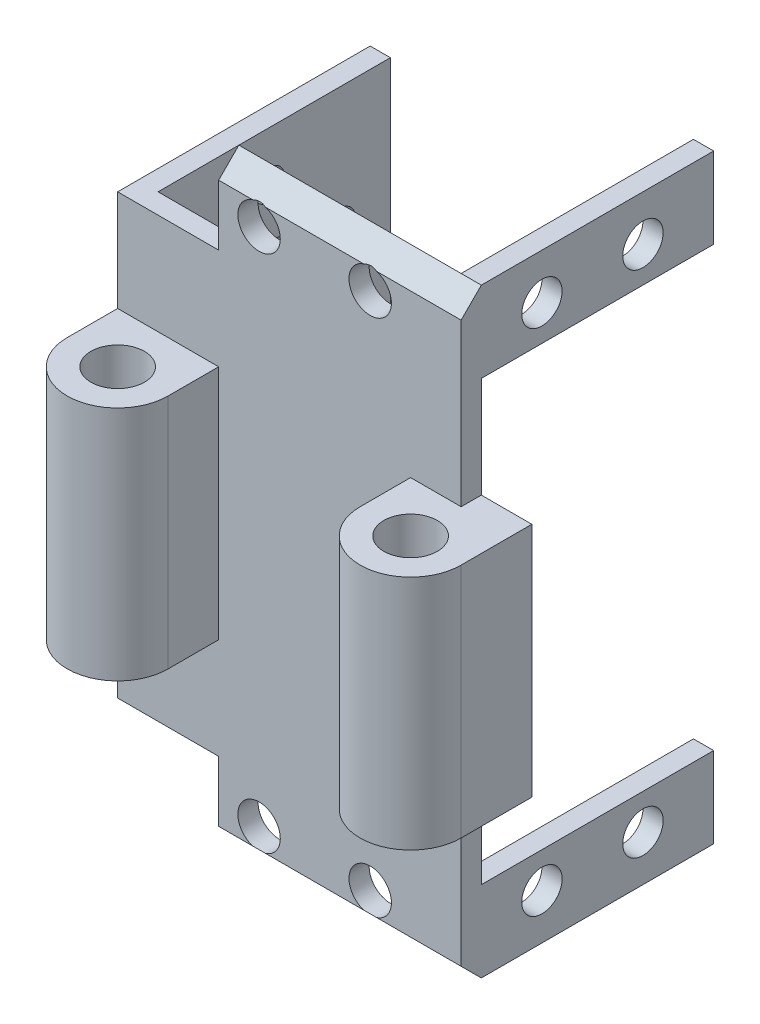
SolidWorks part; units mm, degrees
other "Marquage1"
sketch "Esquisse16" plane through (-20.25, -32.4, -23) normal (-0.063, -0.2594, -0.9637) x (0.9802, 0.1655, -0.1086)
ref_plane "Plan de face" through (0, 0, 0) normal (0, 0, 1) x (1, 0, 0)
ref_plane "Plan de dessus" through (0, 0, 0) normal (0, 1, 0) x (1, 0, 0)
ref_plane "Plan de droite" through (0, 0, 0) normal (1, 0, 0) x (0, 0, -1)
sketch "Esquisse1" plane through (0, 0, 0) normal (0, 0, 1) x (1, 0, 0)
  line L0 (8.75, 17) -> (8.75, 19)
  line L4 (16.25, -22.4) -> (16.25, 17)
  line L5 (8.75, 19) -> (-10.25, 19) construction
  line L6 (-10.25, 19) -> (-20.25, 19)
  line L7 (8.75, 19) -> (13.75, 19)
  line L8 (13.75, 19) -> (13.75, 27)
  line L9 (13.75, 27) -> (-10.25, 27)
  line L10 (-10.25, 27) -> (-10.25, 19)
  line L11 (-20.25, -2.7) -> (16.25, -2.7) construction
  line L17 (8.75, 17) -> (16.25, 17)
  line L20 (-20.25, 19) -> (-20.25, -24.4)
  line L21 (8.75, -22.4) -> (16.25, -22.4)
  line L22 (-10.25, -32.4) -> (-10.25, -24.4)
  line L23 (13.75, -32.4) -> (-10.25, -32.4)
  line L24 (13.75, -24.4) -> (13.75, -32.4)
  line L25 (8.75, -24.4) -> (13.75, -24.4)
  line L26 (-10.25, -24.4) -> (-20.25, -24.4)
  line L27 (8.75, -22.4) -> (8.75, -24.4)
  point P0 (0, 0)
  point P18 (0, -5.4)
  dimension "D1" = 19.7
  dimension "D2" = 21.7
  dimension "D3" = 24
  dimension "D4" = 8
  dimension "D5" = 5
  dimension "D6" = 2
  dimension "D7" = 10
  dimension "D8" = 36.5
extrude "Boss.-Extru.1" add sketch "Esquisse1" along normal blind 2
sketch "Esquisse2" plane through (0, 0, 0) normal (0, 0, -1) x (-1, 0, 0)
  line L0 (18.25, 19) -> (20.25, 19)
  line L1 (20.25, 19) -> (20.25, -24.4) construction
  line L2 (20.25, 19) -> (20.25, -24.4)
  line L3 (20.25, -24.4) -> (18.25, -24.4)
  line L5 (18.25, -24.4) -> (18.25, 19)
  line L9 (20.25, -24.4) -> (10.25, -24.4) construction
  dimension "D1" = 2
  dimension "D2" = 43.4
extrude "Boss.-Extru.2" add sketch "Esquisse2" along normal blind 23
sketch "Esquisse3" plane through (0, 27, 0) normal (0, 1, 0) x (1, 0, 0)
  line L0 (13.75, 0) -> (11.75, 0)
  line L1 (13.75, 0) -> (-10.25, 0) construction
  line L2 (11.75, 0) -> (11.75, 23)
  line L3 (11.75, 23) -> (13.75, 23)
  line L4 (13.75, 23) -> (13.75, 0)
  dimension "D1" = 2
  dimension "D2" = 23
extrude "Boss.-Extru.3" add sketch "Esquisse3" against normal blind 8
sketch "Esquisse8" plane through (0, -32.4, 0) normal (0, -1, 0) x (1, 0, 0)
  line L0 (13.75, 0) -> (11.75, 0)
  line L1 (11.75, 0) -> (11.75, -23)
  line L2 (11.75, -23) -> (13.75, -23)
  line L3 (13.75, -23) -> (13.75, 0)
  dimension "D1" = 2
extrude "Boss.-Extru.5" add sketch "Esquisse8" against normal blind 8
sketch "Esquisse9" plane through (13.75, 0, 0) normal (1, 0, 0) x (0, 0, -1)
  line L0 (-2, 19) -> (-2, 27) construction
  line L1 (-2, 19) -> (23, 19) construction
  line L2 (0, -2.7) -> (21.4042, -2.7) construction
  line L3 (0, -22.4) -> (0, 17) construction
  circle A0 centre (6, 22.5) radius 2
  circle A1 centre (16, 22.5) radius 2
  circle A2 centre (16, -27.9) radius 2
  circle A3 centre (6, -27.9) radius 2
  dimension "D1" = 4
  dimension "D2" = 4
  dimension "D3" = 10
  dimension "D4" = 3.5
  dimension "D5" = 3.5
  dimension "D6" = 8
extrude "Enlèv. mat.-Extru.3" cut sketch "Esquisse9" against normal blind 2
sketch "Esquisse10" plane through (-20.25, 0, 0) normal (-1, 0, 0) x (0, 0, 1)
  line L0 (-23, 19) -> (0, 19) construction
  line L1 (-23, -24.4) -> (-23, 19) construction
  line L2 (-23, -2.7) -> (2, -2.7) construction
  line L3 (2, 19) -> (2, -24.4) construction
  circle A0 centre (-11, 14.1) radius 1.5
  circle A1 centre (-11, 7.1) radius 2.25
  circle A2 centre (-4, 7.1) radius 1.5
  circle A3 centre (-11, 0.1) radius 1.5
  circle A4 centre (-18, 7.1) radius 1.5
  circle A5 centre (-11, -5.5) radius 1.5
  circle A6 centre (-11, -12.5) radius 2.25
  circle A7 centre (-4, -12.5) radius 1.5
  circle A8 centre (-18, -12.5) radius 1.5
  circle A9 centre (-11, -19.5) radius 1.5
  point P17 (-11, 7.1)
  dimension "D1" = 3
  dimension "D2" = 4.5
  dimension "D3" = 4.9
  dimension "D4" = 11.9
  dimension "D5" = 12
  dimension "D6" = 12
  dimension "D7" = 4
extrude "Enlèv. mat.-Extru.4" cut sketch "Esquisse10" against normal blind 2
sketch "Esquisse11" plane through (0, 0, 2) normal (0, 0, 1) x (1, 0, 0)
  line L0 (8.75, 19) -> (-10.25, 19) construction
  line L1 (-0.75, 19) -> (-0.75, 27) construction
  line L2 (13.75, 27) -> (-10.25, 27) construction
  line L3 (-6.25, 23) -> (4.75, 23) construction
  line L4 (16.25, -2.7) -> (-20.25, -2.7) construction
  line L5 (16.25, -22.4) -> (16.25, 17) construction
  line L6 (-20.25, 19) -> (-20.25, -24.4) construction
  circle A0 centre (-6.25, 23) radius 2.1
  circle A1 centre (4.75, 23) radius 2.1
  circle A2 centre (4.75, -28.4) radius 2.1
  circle A3 centre (-6.25, -28.4) radius 2.1
  point P11 (-0.75, 23)
  dimension "D2" = 4.2
  dimension "D3" = 4.2
  dimension "D1" = 11
extrude "Enlèv. mat.-Extru.5" cut sketch "Esquisse11" against normal up to next
sketch "Esquisse13" plane through (0, -24.4, 0) normal (0, -1, 0) x (1, 0, 0)
  line L0 (18.75, 12) -> (8.75, 2) construction
  line L1 (-10.25, 0) -> (-20.25, 0)
  line L2 (-10.25, 0) -> (-10.25, 7)
  line L4 (-20.25, 0) -> (-20.25, 7)
  line L5 (8.75, 0) -> (18.75, 0)
  line L6 (8.75, 0) -> (8.75, 7)
  line L8 (18.75, 0) -> (18.75, 7)
  line L9 (-10.25, 2) -> (-20.25, 12) construction
  circle A0 centre (13.75, 7) radius 2.65
  circle A1 centre (-15.25, 7) radius 2.65
  arc A2 (18.75, 7) -> (8.75, 7) centre (13.75, 7) ccw
  arc A3 (-10.25, 7) -> (-20.25, 7) centre (-15.25, 7) ccw
  dimension "D5" = 5.3
  dimension "D6" = 5.3
extrude "Boss.-Extru.6" add sketch "Esquisse13" against normal up to surface (43.4 mm away) up to face at (-16.25, 19, -7)
sketch "Esquisse14" plane through (0, 19, 0) normal (0, 1, 0) x (1, 0, 0)
  line L0 (13.75, -2) -> (13.75, 23) construction
  line L1 (-10.25, -2) -> (-20.25, -2)
  line L2 (-10.25, -2) -> (-10.25, -14.2809)
  line L3 (-10.25, -14.2809) -> (-24.6932, -14.2809)
  line L4 (-24.6932, -2) -> (-24.6932, -14.2809)
  line L5 (8.75, -2) -> (13.75, -2)
  line L6 (8.75, -2) -> (8.75, -13.0445)
  line L7 (8.75, -13.0445) -> (27.1122, -13.0445)
  line L8 (27.1122, -2) -> (27.1122, -13.0445)
  line L9 (13.75, 5.1811) -> (21.1699, 5.1811)
  line L10 (13.75, 5.1811) -> (13.75, -2)
  line L12 (21.1699, 5.1811) -> (21.1699, -2)
  line L13 (-20.25, -7) -> (-20.25, 23) construction
  line L14 (-20.25, 7.2947) -> (-22.7789, 7.2947)
  line L15 (-20.25, 7.2947) -> (-20.25, -2)
  line L17 (-22.7789, 7.2947) -> (-22.7789, -2)
  line L18 (-22.7789, -2) -> (-24.6932, -2)
  line L19 (21.1699, -2) -> (27.1122, -2)
extrude "Enlèv. mat.-Extru.6" cut sketch "Esquisse14" against normal blind 10
sketch "Esquisse15" plane through (0, -24.4, 0) normal (0, -1, 0) x (1, 0, 0)
  line L0 (-10.25, 2) -> (13.75, 2) construction
  line L1 (-7.7651, 2) -> (-20.25, 2)
  line L2 (-7.7651, 2) -> (-7.7651, 15.3144)
  line L3 (-7.7651, 15.3144) -> (-33.1794, 15.3144)
  line L4 (-33.1794, 2) -> (-33.1794, 15.3144)
  line L5 (13.75, 2) -> (13.75, -23) construction
  line L6 (6.631, 2) -> (13.75, 2)
  line L7 (6.631, 2) -> (6.631, 15.3144)
  line L8 (6.631, 15.3144) -> (24.5342, 15.3144)
  line L9 (24.5342, 2) -> (24.5342, 15.3144)
  line L11 (22.3035, 2) -> (22.3035, -6.0207)
  line L12 (22.3035, -6.0207) -> (13.75, -6.0207)
  line L13 (13.75, 2) -> (13.75, -6.0207)
  line L14 (-20.25, 7) -> (-20.25, -23) construction
  line L15 (-20.25, -7.2219) -> (-27.574, -7.2219)
  line L16 (-20.25, -7.2219) -> (-20.25, 2)
  line L18 (-27.574, -7.2219) -> (-27.574, 2)
  line L19 (-27.574, 2) -> (-33.1794, 2)
  line L20 (22.3035, 2) -> (24.5342, 2)
extrude "Enlèv. mat.-Extru.7" cut sketch "Esquisse15" against normal blind 10
chamfer "Chanfrein1" distance 2 angle 45 1 edges at (1.75, 27, 2)
chamfer "Chanfrein2" distance 2 angle 45 1 edges at (1.75, -32.4, 2)
